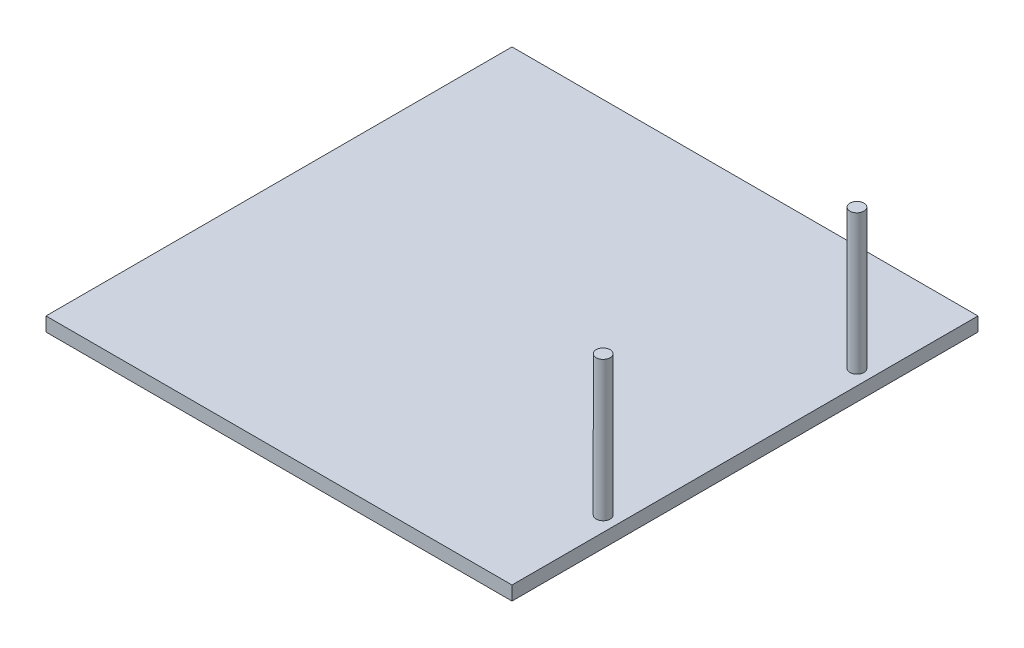
SolidWorks part; units mm, degrees
ref_plane "Front Plane" through (0, 0, 0) normal (0, 0, 1) x (1, 0, 0)
ref_plane "Top Plane" through (0, 0, 0) normal (0, 1, 0) x (1, 0, 0)
ref_plane "Right Plane" through (0, 0, 0) normal (1, 0, 0) x (0, 0, -1)
sketch "Sketch1" plane through (0, 0, 0) normal (0, 1, 0) x (1, 0, 0)
  line L1 (-50, -50) -> (50, -50)
  line L2 (-50, -50) -> (-50, 50)
  line L3 (-50, 50) -> (50, 50)
  line L4 (50, -50) -> (50, 50)
  line L5 (-50, -50) -> (50, 50) construction
  line L6 (-50, 50) -> (50, -50) construction
  point P0 (0, 0)
  dimension "D1" = 100
  dimension "D2" = 100
extrude "Boss-Extrude1" add sketch "Sketch1" along normal blind 3
sketch "Sketch2" plane through (0, 3, 0) normal (0, 1, 0) x (1, 0, 0)
  line L0 (-70.6517, 0) -> (70.6517, 0) construction
  circle A0 centre (46.7897, 27.2349) radius 1.5
  circle A1 centre (46.7897, -27.2349) radius 1.5
  point P4 (46.7897, -27.2349)
  point P8 (0, 0)
  dimension "D1" = 3
extrude "Boss-Extrude2" add sketch "Sketch2" along normal blind 30
